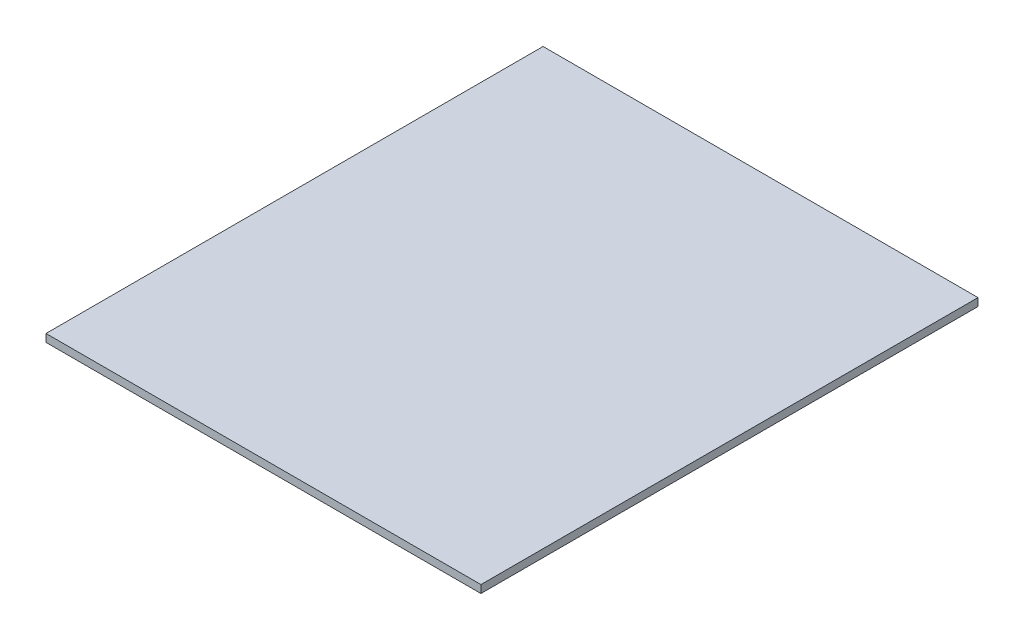
SolidWorks part; units mm, degrees
material "Maple"
ref_plane "Front Plane" through (0, 0, 0) normal (0, 0, 1) x (1, 0, 0)
ref_plane "Top Plane" through (0, 0, 0) normal (0, 1, 0) x (1, 0, 0)
ref_plane "Right Plane" through (0, 0, 0) normal (1, 0, 0) x (0, 0, -1)
sketch "Sketch1" plane through (0, 0, 0) normal (0, 1, 0) x (1, 0, 0)
  line L1 (0, 0) -> (355.6, 0)
  line L2 (0, 0) -> (0, 406.4)
  line L3 (0, 406.4) -> (355.6, 406.4)
  line L4 (355.6, 0) -> (355.6, 406.4)
  dimension "D1" = 406.4
  dimension "D2" = 355.6
extrude "Boss-Extrude1" add sketch "Sketch1" along normal blind 6.35
